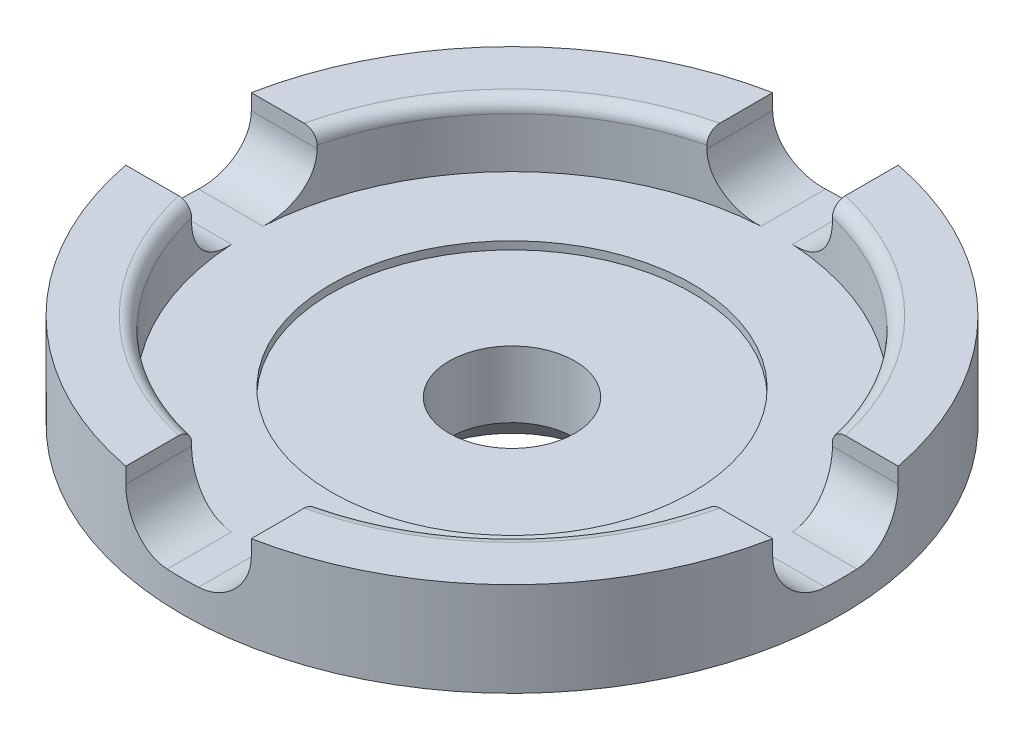
SolidWorks part; units mm, degrees
ref_plane "Front plane" through (0, 0, 0) normal (0, 0, 1) x (1, 0, 0)
ref_plane "Top plane" through (0, 0, 0) normal (0, 1, 0) x (1, 0, 0)
ref_plane "Right plane" through (0, 0, 0) normal (1, 0, 0) x (0, 0, -1)
ref_axis "Axis X" through (0, 0, 0) along (1, 0, 0)
ref_axis "Axis Y" through (0, 0, 0) along (0, 1, 0)
ref_axis "Axis Z" through (0, 0, 0) along (0, 0, 1)
sketch "Sketch1" plane through (0, 0, 0) normal (0, 1, 0) x (1, 0, 0)
  circle A0 centre (0, 0) radius 10.5
  dimension "D1" = 21
extrude "Extrude1" add sketch "Sketch1" along normal blind 1
sketch "Sketch6" plane through (0, 1, 0) normal (0, 1, 0) x (1, 0, 0)
  line L0 (-2, 10.3078) -> (-2, 8.2099)
  line L1 (2, 10.3078) -> (2, 8.2099)
  line L2 (0, 10) -> (0, 0) construction
  line L3 (10.3078, 2) -> (8.2099, 2)
  line L4 (10.3078, -2) -> (8.2099, -2)
  line L5 (2, -10.3078) -> (2, -8.2099)
  line L6 (-2, -10.3078) -> (-2, -8.2099)
  line L7 (-10.3078, -2) -> (-8.2099, -2)
  line L8 (-10.3078, 2) -> (-8.2099, 2)
  arc A0 (-2, 8.2099) -> (-8.2099, 2) centre (0, 0) ccw
  arc A1 (-2, 10.3078) -> (-10.3078, 2) centre (0, 0) ccw
  circle A2 centre (0, 0) radius 10.5 construction
  arc A3 (8.2099, 2) -> (2, 8.2099) centre (0, 0) ccw
  arc A4 (10.3078, 2) -> (2, 10.3078) centre (0, 0) ccw
  arc A5 (-8.2099, -2) -> (-2, -8.2099) centre (0, 0) ccw
  arc A6 (-10.3078, -2) -> (-2, -10.3078) centre (0, 0) ccw
  arc A7 (2, -8.2099) -> (8.2099, -2) centre (0, 0) ccw
  arc A8 (2, -10.3078) -> (10.3078, -2) centre (0, 0) ccw
  point P11 (2, 9.2588)
  point P27 (0, 0)
  dimension "D1" = 16.9
  dimension "D2" = 4
  dimension "D3" = 4
extrude "Extrude6" add sketch "Sketch6" along normal blind 2
sketch "Sketch9" plane through (0, 1, 0) normal (0, 1, 0) x (1, 0, 0)
  circle A0 centre (0, 0) radius 5.75
  dimension "D1" = 11.5
extrude "Extrude9" cut sketch "Sketch9" against normal blind 0.25
sketch "Sketch7" plane through (0, 0, 0) normal (0, -1, 0) x (1, 0, 0)
  circle A0 centre (0, 0) radius 4.9
  dimension "D1" = 9.8
extrude "Extrude7" add sketch "Sketch7" along normal blind 2.3667
sketch "Sketch8" plane through (0, -2.3667, 0) normal (0, -1, 0) x (1, 0, 0)
  circle A0 centre (0, 0) radius 2
  dimension "D1" = 4
extrude "Extrude8" cut sketch "Sketch8" against normal through all
fillet "Fillet2" radius 0.4 5 edges at (0, -2.3667, -4.9) (-5.9751, 3, -5.9751) (-5.9751, 3, 5.9751) (5.9751, 3, 5.9751) (5.9751, 3, -5.9751)
chamfer "Chamfer2" distance 1 angle 45 1 edges at (0, -2.3667, -2)
fillet "Fillet3" radius 1.5 8 edges at (9.2588, 1, 2) (9.2588, 1, -2) (2, 1, -9.2588) (-2, 1, -9.2588) (-2, 1, 9.2588) (2, 1, 9.2588) (-9.2588, 1, 2) (-9.2588, 1, -2)
equation "\"motor_D\"= 30'Motor diameter"
equation "\"motor_H\"= 13'Motor heigh"
equation "\"motor_d1\"= 25.4558'Seating diameter of screws on the fixed part of the motor"
equation "\"motor_s1\"= 2'Screws diameter on the fixed part of motor"
equation "\"motor_d2\"= 0'Seating diameter of screws on the moving part of the motor (if this parameter is not determine, write 0)"
equation "\"motor_a2\"= 10'Seating parameter in rectangle of screws on the moving part of the motor"
equation "\"motor_b2\"= 22'Seating parameter in rectangle of screws on the moving part of the motor"
equation "\"motor_s2\"= 2'Screws diameter on the moving part of motor"
equation "\"motor_cmd\"= 12'Central magnet mount diameter"
equation "\"motor_cmh\"= 1.4'Central magnet mount heigh (if not write 0)"
equation "\"motor_Dc\"= 5'Central hole diameter of motor"
equation "\"motor_whR\"= 10'Distance from center of motor to wires"
equation "\"bearing_d1\"= 6'Bearing inner diameter"
equation "\"bearing_d2\"= 17'Bearing external diameter"
equation "\"bearing h\"= 6'Bearing heigh"
equation "\"pin_d\"= 2'Pin diameter"
equation "\"pin_h\"= 12'Pin heigh"
equation "\"magnet_d1\"= 5'Magnet inner diameter"
equation "\"magnet_d2\"= 9.5'Magnet external diameter"
equation "\"magnet_h\"= 3'Magnet heigh"
equation "\"print_offset\"= 0.2'Offset for printing holes"
equation "\"ft_sensor_d1\"= 9.8"
equation "\"ft_sensor_d2\"= 24.9"
equation "\"ft_sensor_d3\"= 22.6'Inner diameter of "
equation "\"ft_sensor_h\"= 7.1"
equation "\"ft_sensor_whD\" = 5"
equation "\"D1@Sketch1\"=\"bearing_d2\"+4"
equation "\"D1@Sketch6\"=\"bearing_d2\"-\"print_offset\"*0.5"
equation "\"D1@Extrude6\"=\"bearing h\"/3"
equation "\"D1@Sketch7\"=\"ft_sensor_d1\""
equation "\"D1@Extrude7\"=\"ft_sensor_h\"/3"
equation "\"D1@Sketch9\"=(\"bearing_d1\"+\"bearing_d2\")/2"
